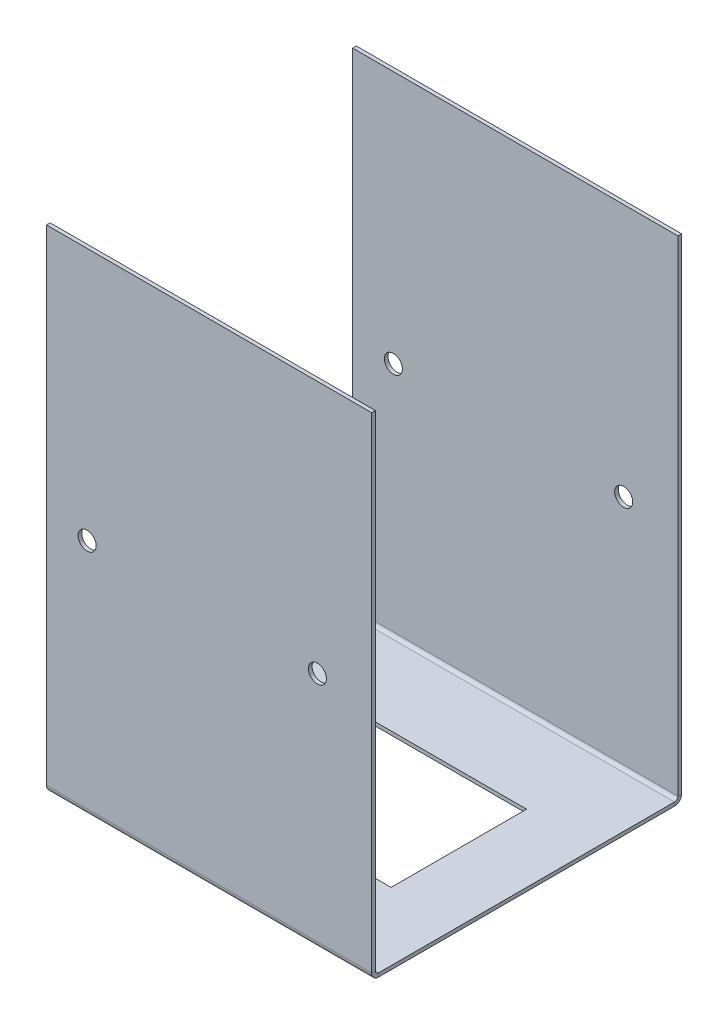
SolidWorks part; units mm, degrees
note: The reader was unsure of these and kept them because the rebuilt part matched: flange length of "Edge-Flange1".
ref_plane "Front Plane" through (0, 0, 0) normal (0, 0, 1) x (1, 0, 0)
ref_plane "Top Plane" through (0, 0, 0) normal (0, 1, 0) x (1, 0, 0)
ref_plane "Right Plane" through (0, 0, 0) normal (1, 0, 0) x (0, 0, -1)
sketch "Sketch1" plane through (0, 0, 0) normal (0, 1, 0) x (1, 0, 0)
  line L1 (0, 0) -> (72, 0)
  line L2 (0, 0) -> (0, 67)
  line L3 (0, 67) -> (72, 67)
  line L4 (72, 0) -> (72, 67)
  dimension "D1" = 72
  dimension "D2" = 67
base flange "Base-Flange1" sketch "Sketch1" thickness 0.81 reverse thickness direction no parameters "D1"=0.7366
edge flange "Edge-Flange1" sketch "Sketch10" flange profiles "Sketch10", "Sketch11" flange angle 90 flange length 109 flange position material outside bend radius 0.7366 thickness 0.81 relief rectangular parameters "D6"=10, "D8"=1
sketch "Sketch10" plane through (0, 0, 0) normal (0, 0, 1) x (1, 0, 0)
  line L0 (0, 0) -> (72, 0) construction
  line L1 (0, 0) -> (72, 0)
  line L2 (0, 0) -> (0, 108.19)
  line L3 (0, 108.19) -> (72, 108.19)
  line L4 (72, 108.19) -> (72, 0)
sketch "Sketch11" plane through (0, 0, -67) normal (0, 0, -1) x (-1, 0, 0)
  line L0 (-72, 0) -> (0, 0) construction
  line L1 (-72, 0) -> (0, 0)
  line L2 (-72, 0) -> (-72, 108.19)
  line L3 (-72, 108.19) -> (0, 108.19)
  line L4 (0, 108.19) -> (0, 0)
bend "EdgeBend1" bend radius 0.7366 bend angle 90 parameters "D5"=1
bend "EdgeBend2" bend radius 0.7366 bend angle 90 parameters "D5"=2
sketch "Sketch12" plane through (0, 0, 0) normal (0, 1, 0) x (1, 0, 0)
  line L0 (0, 66.2634) -> (0, 0.7366) construction
  line L1 (15, 18.5) -> (57, 18.5)
  line L2 (15, 18.5) -> (15, 48.5)
  line L3 (15, 48.5) -> (57, 48.5)
  line L4 (57, 18.5) -> (57, 48.5)
  line L5 (72, 0.7366) -> (72, 66.2634) construction
  line L6 (0, 33.5) -> (72, 33.5) construction
  dimension "D1" = 15
  dimension "D2" = 15
  dimension "D3" = 30
extrude "Cut-Extrude1" cut sketch "Sketch12" against normal up to next normal cut yes
sketch "Sketch13" plane through (0, 0, -67.81) normal (0, 0, -1) x (-1, 0, 0)
  line L0 (0, 0.7366) -> (-72, 0.7366) construction
  line L1 (0, 0.7366) -> (0, 108.19) construction
  line L2 (-34.5, 108.19) -> (-34.5, 0.7366) construction
  line L4 (0, 108.19) -> (-72, 108.19) construction
  circle A0 centre (-9, 52.1466) radius 2
  circle A1 centre (-60, 52.1466) radius 2
  dimension "D1" = 51.41
  dimension "D3" = 4
  dimension "D2" = 9
  dimension "D4" = 34.5
extrude "Cut-Extrude2" cut sketch "Sketch13" against normal up to surface (68.62 mm away) normal cut yes up to face at (36, 54.4633, 0.81)
sketch "Bend-Lines1" plane through (0, 0, 0) normal (0, 1, 0) x (1, 0, 0)
sketch "Bounding-Box1" plane through (0, 0, 0) normal (0, 1, 0) x (1, 0, 0)
sheet metal parameters "Sheet-Metal1" thickness 0.81 parameters "D1"=0.7366
flat pattern "Flat-Pattern1" [suppressed]
sketch "Bend-Lines2" plane through (0, 0, 0) normal (0, 1, 0) x (1, 0, 0)
sketch "Bounding-Box2" [suppressed] plane through (0, 0, 0) normal (0, 1, 0) x (1, 0, 0)
sheet metal parameters "Sheet-Metal2" thickness 0.81 parameters "D1"=0.7366
flat pattern "Flat-Pattern1" [suppressed]
sketch "Bend-Lines2" plane through (0, 0, 0) normal (0, 1, 0) x (1, 0, 0)
sketch "Bounding-Box2" [suppressed] plane through (0, 0, 0) normal (0, 1, 0) x (1, 0, 0)
bend of the flat pattern "Flatten-<EdgeBend1>1"
bend of the flat pattern "Flatten-<EdgeBend2>1"
sheet metal parameters "Sheet-Metal3" thickness 0.81 parameters "D1"=0.7366
flat pattern "Flat-Pattern1" [suppressed]
sketch "Bend-Lines2" plane through (0, 0, 0) normal (0, 1, 0) x (1, 0, 0)
sketch "Bounding-Box2" [suppressed] plane through (0, 0, 0) normal (0, 1, 0) x (1, 0, 0)
bend of the flat pattern "Flatten-<EdgeBend1>1"
bend of the flat pattern "Flatten-<EdgeBend2>1"
sheet metal parameters "Sheet-Metal4" thickness 0.81 parameters "D1"=0.7366
flat pattern "Flat-Pattern1" [suppressed]
sketch "Bend-Lines2" plane through (0, 0, 0) normal (0, 1, 0) x (1, 0, 0)
sketch "Bounding-Box2" [suppressed] plane through (0, 0, 0) normal (0, 1, 0) x (1, 0, 0)
bend of the flat pattern "Flatten-<EdgeBend1>1"
bend of the flat pattern "Flatten-<EdgeBend2>1"
